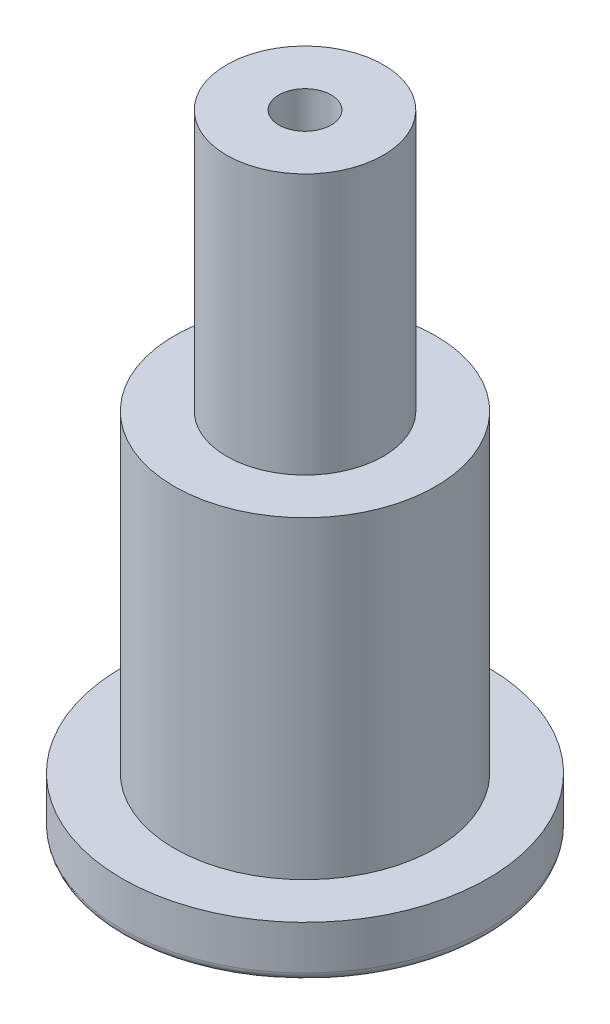
SolidWorks part; units mm, degrees
material "PET"
ref_plane "Front Plane" through (0, 0, 0) normal (0, 0, 1) x (1, 0, 0)
ref_plane "Top Plane" through (0, 0, 0) normal (0, 1, 0) x (1, 0, 0)
ref_plane "Right Plane" through (0, 0, 0) normal (1, 0, 0) x (0, 0, -1)
ref_axis "X-Axis" through (-88.99, 0, 0) along (1, 0, 0)
ref_axis "Y-Axis" through (0, 55, 0) along (0, -1, 0)
ref_axis "Z-Axis" through (0, 0, -88.99) along (0, 0, 1)
sketch "Sketch1" plane through (0, 0, 0) normal (0, 1, 0) x (1, 0, 0)
  circle A0 centre (0, 0) radius 5.5562
  dimension "D1" = 11.1125
extrude "Boss-Extrude1" add sketch "Sketch1" along normal blind 1.5875
ref_plane "Plane1" through (0, 1.5875, 0) normal (0, 1, 0) x (1, 0, 0)
sketch "Sketch2" plane through (0, 1.5875, 0) normal (0, 1, 0) x (1, 0, 0)
  circle A0 centre (0, 0) radius 3.9688
  dimension "D1" = 7.9375
extrude "Boss-Extrude2" add sketch "Sketch2" along normal blind 9.525
ref_plane "Plane2" through (0, 11.1125, 0) normal (0, 1, 0) x (1, 0, 0)
sketch "Sketch3" plane through (0, 11.1125, 0) normal (0, 1, 0) x (1, 0, 0)
  circle A0 centre (0, 0) radius 2.3813
  dimension "D1" = 4.7625
extrude "Extrude-Thin2" add sketch "Sketch3" along normal blind 7.9248 thin thin type one direction reverse wall 1.5875
fillet "Fillet1" radius 0.254 1 edges at (0, 0, 5.5562)
